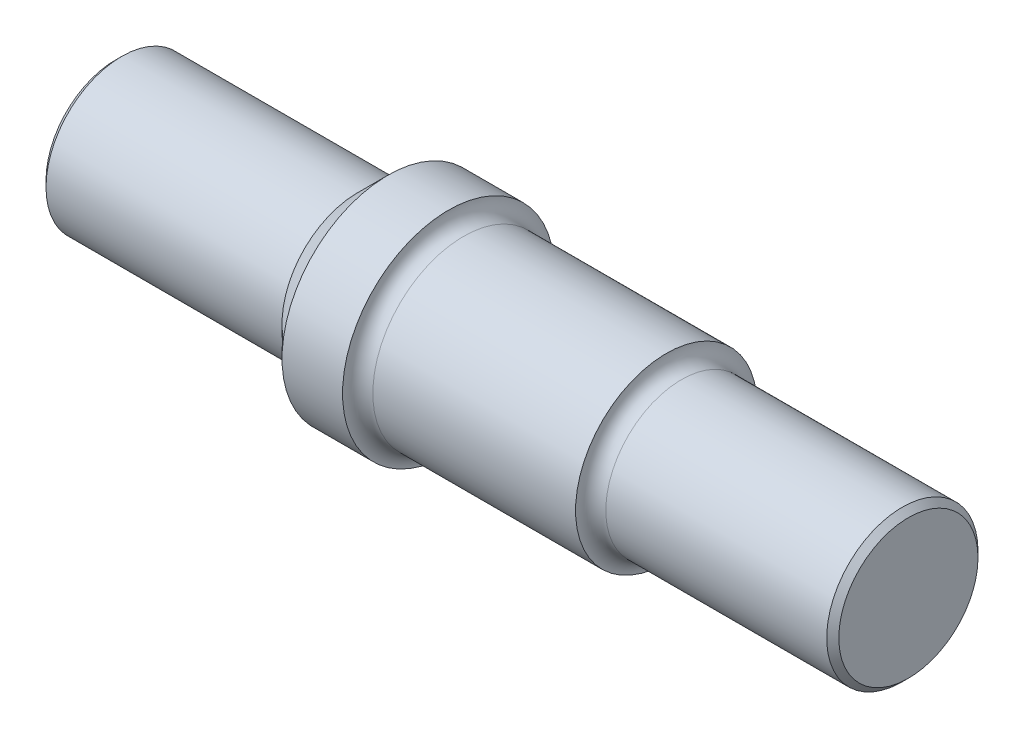
SolidWorks part; units mm, degrees
ref_plane "Front Plane" through (0, 0, 0) normal (0, 0, 1) x (1, 0, 0)
ref_plane "Top Plane" through (0, 0, 0) normal (0, 1, 0) x (1, 0, 0)
ref_plane "Right Plane" through (0, 0, 0) normal (1, 0, 0) x (0, 0, -1)
sketch "Sketch1" plane through (0, 0, 0) normal (0, 0, 1) x (1, 0, 0)
  line L0 (0, 0) -> (0, 12.5)
  line L1 (0, 12.5) -> (40, 12.5)
  line L2 (40, 12.5) -> (45, 17.5)
  line L3 (45, 17.5) -> (55, 17.5)
  line L4 (55, 17.5) -> (55, 15)
  line L5 (55, 15) -> (91, 15)
  line L6 (91, 15) -> (91, 12.5)
  line L7 (91, 12.5) -> (131, 12.5)
  line L8 (131, 12.5) -> (131, 0)
  line L9 (131, 0) -> (0, 0)
  point P3 (20, 12.5)
  point P12 (73, 15)
  point P13 (111, 12.5)
  dimension "D1" = 12.5
  dimension "D2" = 40
  dimension "D3" = 40
  dimension "D4" = 36
  dimension "D5" = 10
  dimension "D6" = 45
  dimension "D7" = 2.5
  dimension "D8" = 2.5
  dimension "D9" = 91
  dimension "D10" = 53
  dimension "D11" = 38
revolve "Revolve1" add sketch "Sketch1" angle 360 about L9
fillet "Fillet1" radius 2.5 2 edges at (91, 0, -12.5) (55, 0, -15)
chamfer "Chamfer2" distance 1 angle 45 2 edges at (131, 0, -12.5) (0, 0, -12.5)
